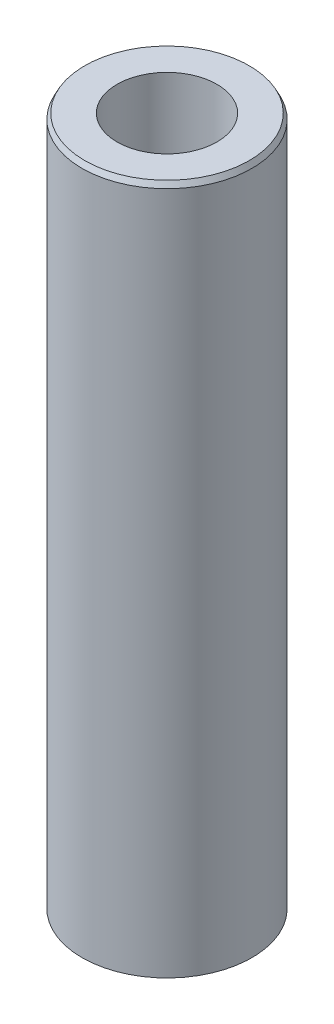
SolidWorks part; units mm, degrees
ref_plane "Front Plane" through (0, 0, 0) normal (0, 0, 1) x (1, 0, 0)
ref_plane "Top Plane" through (0, 0, 0) normal (0, 1, 0) x (1, 0, 0)
ref_plane "Right Plane" through (0, 0, 0) normal (1, 0, 0) x (0, 0, -1)
sketch "Sketch1" plane through (0, 0, 0) normal (0, 1, 0) x (1, 0, 0)
  circle A0 centre (0, 0) radius 47.5
  dimension "SHAFT_OD" = 95
extrude "Boss-Extrude1" add sketch "Sketch1" along normal blind 386.5801
sketch "Sketch2" plane through (0, 0, 0) normal (0, 1, 0) x (1, 0, 0)
  circle A0 centre (0, 0) radius 27.9352
  dimension "BORE_D" = 55.8703
extrude "Cut-Extrude1" cut sketch "Sketch2" along normal through all
chamfer "Chamfer1" distance 3.0016 angle 27.067 2 edges at (0, 386.5801, 47.5) (0, 0, 47.5) first distance on face at (0, 386.5801, 47.5) first distance on face at (0, 0, 27.9352)
